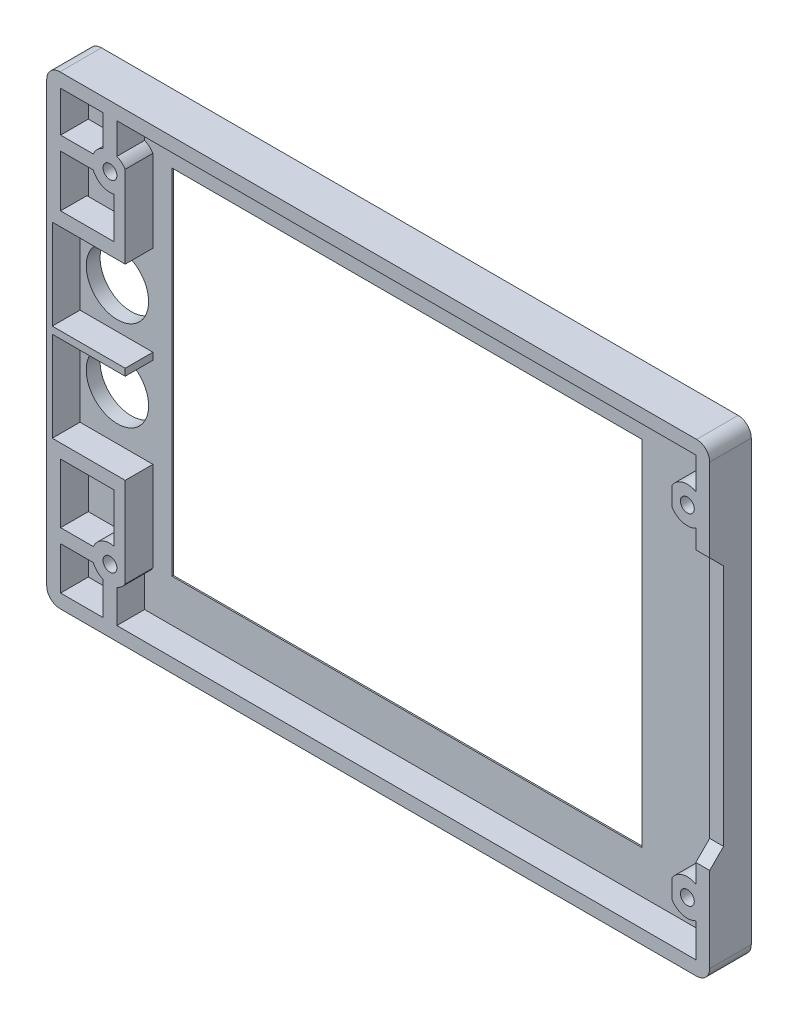
SolidWorks part; units mm, degrees
ref_plane "Спереди" through (0, 0, 0) normal (0, 0, 1) x (1, 0, 0)
ref_plane "Сверху" through (0, 0, 0) normal (0, 1, 0) x (1, 0, 0)
ref_plane "Справа" through (0, 0, 0) normal (1, 0, 0) x (0, 0, -1)
other "Configuration Table"
sketch "Эскиз1" plane through (0, 0, 0) normal (0, 0, 1) x (1, 0, 0)
  line L0 (-33.735, 25.6063) -> (34.065, 25.6063)
  line L1 (34.065, -25.3937) -> (34.065, 25.6063)
  line L2 (-45.825, 31.5375) -> (-45.825, 25.6776)
  line L3 (-39.7018, 31.5375) -> (-45.825, 31.5375)
  line L4 (-39.7018, 31.5375) -> (-39.7018, 27.0776)
  line L5 (-45.825, 23.6776) -> (-41.1018, 23.6776)
  line L6 (-45.825, 23.6776) -> (-45.825, 15.4128)
  line L7 (-37.1018, 22.6282) -> (-37.1018, 15.4128)
  line L8 (47.825, -31.6375) -> (47.825, -19.3686)
  line L9 (47.825, -19.3686) -> (45.825, -19.3686)
  line L10 (45.825, -19.3686) -> (45.825, -22.0746)
  line L11 (45.825, -26.6627) -> (45.825, -31.5375)
  line L12 (45.825, -31.5375) -> (-37.7018, -31.5375)
  line L13 (-37.7018, -31.5375) -> (-37.7018, -26.7686)
  line L14 (-36.1018, -24.3678) -> (-36.1018, 24.6776)
  line L15 (-37.7018, 27.0776) -> (-37.7018, 31.5375)
  line L16 (-37.7018, 31.5375) -> (45.825, 31.5375)
  line L17 (45.825, 31.5375) -> (45.825, 26.9716)
  line L18 (45.825, 22.3836) -> (45.825, 19.6776)
  line L19 (45.825, 19.6776) -> (47.825, 19.6776)
  line L20 (47.825, 19.6776) -> (47.825, 31.6375)
  line L21 (45.925, 33.5375) -> (-45.925, 33.5375)
  line L22 (-47.825, 31.6375) -> (-47.825, -31.6375)
  line L23 (-45.925, -33.5375) -> (45.925, -33.5375)
  line L24 (-37.1018, 15.4128) -> (-45.825, 15.4128)
  line L25 (-36.5018, 1.2128) -> (-47.025, 1.2128)
  line L26 (-47.025, 0.2057) -> (-36.5018, 0.2057)
  line L27 (-47.025, 14.2128) -> (-47.025, 1.2128)
  line L28 (-47.025, 0.2057) -> (-47.025, -12.7943)
  line L29 (-33.735, 25.6063) -> (-33.735, -25.3937)
  line L30 (34.065, -25.3937) -> (-33.735, -25.3937)
  line L31 (-47.025, -12.7943) -> (-36.5018, -12.7943)
  line L32 (-45.825, -13.9943) -> (-37.1018, -13.9943)
  line L33 (-45.825, -13.9943) -> (-45.825, -23.3686)
  line L34 (-41.1018, -23.3686) -> (-45.825, -23.3686)
  line L35 (-37.1018, -13.9943) -> (-37.1018, -22.3192)
  line L36 (-45.825, -25.3686) -> (-41.1018, -25.3686)
  line L37 (-45.825, -25.3686) -> (-45.825, -31.5375)
  line L38 (-39.7018, -26.7686) -> (-39.7018, -31.5375)
  line L39 (-45.825, -31.5375) -> (-39.7018, -31.5375)
  line L40 (45.825, 17.6776) -> (45.825, 19.6776)
  line L41 (47.825, 19.6776) -> (47.825, 17.6776)
  line L42 (45.825, 17.6776) -> (45.825, -17.3686)
  line L43 (45.825, -17.3686) -> (47.825, -17.3686)
  line L44 (47.825, -17.3686) -> (47.825, 17.6776)
  line L45 (47.825, 17.6776) -> (45.825, 17.6776)
  line L46 (45.825, -19.3686) -> (45.825, -17.3686)
  line L47 (47.825, -17.3686) -> (47.825, -19.3686)
  line L48 (-36.5018, 14.2128) -> (-47.025, 14.2128)
  circle A0 centre (44.6013, 24.6776) radius 1
  circle A1 centre (-38.7018, 24.6776) radius 1
  arc A2 (-39.7018, 27.0776) -> (-41.1018, 25.6776) centre (-38.7018, 24.6776) ccw
  arc A3 (-41.1018, 23.6776) -> (-37.1018, 22.6282) centre (-38.7018, 24.6776) ccw
  arc A4 (45.825, -22.0746) -> (45.825, -26.6627) centre (44.6013, -24.3686) ccw
  arc A5 (-37.7018, -26.7686) -> (-36.1018, -24.3678) centre (-38.7018, -24.3686) ccw
  arc A6 (-36.1018, 24.6776) -> (-37.7018, 27.0776) centre (-38.7018, 24.6776) ccw
  arc A7 (45.825, 26.9716) -> (45.825, 22.3836) centre (44.6013, 24.6776) ccw
  arc A8 (47.825, 31.6375) -> (45.925, 33.5375) centre (45.925, 31.6375) ccw
  arc A9 (-45.925, 33.5375) -> (-47.825, 31.6375) centre (-45.925, 31.6375) ccw
  arc A10 (-47.825, -31.6375) -> (-45.925, -33.5375) centre (-45.925, -31.6375) ccw
  arc A11 (45.925, -33.5375) -> (47.825, -31.6375) centre (45.925, -31.6375) ccw
  circle A12 centre (-41.625, 7.2128) radius 4.5
  circle A13 centre (-41.625, -5.7943) radius 4.5
  arc A14 (-37.1018, -22.3192) -> (-41.1018, -23.3686) centre (-38.7018, -24.3686) ccw
  circle A15 centre (-38.7018, -24.3686) radius 1
  arc A16 (-41.1018, -25.3686) -> (-39.7018, -26.7686) centre (-38.7018, -24.3686) ccw
  circle A17 centre (44.6013, -24.3686) radius 1
sketch "Эскиз2" plane through (0, 0, 0) normal (0, 0, 1) x (1, 0, 0)
  line L0 (34.065, -25.3937) -> (-33.735, -25.3937) construction
  line L1 (34.065, -25.3937) -> (34.065, 25.6063) construction
  line L2 (-33.735, 25.6063) -> (34.065, 25.6063) construction
  line L3 (-33.735, 25.6063) -> (-33.735, -25.3937) construction
  line L4 (-47.825, 31.6375) -> (-47.825, -31.6375) construction
  line L5 (-45.925, -33.5375) -> (45.925, -33.5375) construction
  line L6 (47.825, -31.6375) -> (47.825, -19.3686) construction
  line L7 (47.825, -17.3686) -> (47.825, 17.6776) construction
  line L8 (47.825, 19.6776) -> (47.825, 31.6375) construction
  line L9 (45.925, 33.5375) -> (-45.925, 33.5375) construction
  line L10 (34.065, -25.3937) -> (-33.735, -25.3937)
  line L11 (34.065, -25.3937) -> (34.065, 25.6063)
  line L12 (-33.735, 25.6063) -> (34.065, 25.6063)
  line L13 (-33.735, 25.6063) -> (-33.735, -25.3937)
  line L14 (-47.825, 31.6375) -> (-47.825, -31.6375)
  line L15 (-45.925, -33.5375) -> (45.925, -33.5375)
  line L16 (47.825, -31.6375) -> (47.825, -19.3686)
  line L17 (47.825, -17.3686) -> (47.825, 17.6776)
  line L18 (47.825, 19.6776) -> (47.825, 31.6375)
  line L19 (45.925, 33.5375) -> (-45.925, 33.5375)
  line L20 (47.825, 19.6776) -> (47.825, 17.6776) construction
  line L21 (47.825, 19.6776) -> (47.825, 17.6776)
  line L22 (47.825, -17.3686) -> (47.825, -19.3686) construction
  line L23 (47.825, -17.3686) -> (47.825, -19.3686)
  arc A0 (47.825, 31.6375) -> (45.925, 33.5375) centre (45.925, 31.6375) ccw construction
  arc A1 (47.825, 31.6375) -> (45.925, 33.5375) centre (45.925, 31.6375) ccw
  arc A2 (-45.925, 33.5375) -> (-47.825, 31.6375) centre (-45.925, 31.6375) ccw construction
  arc A3 (-45.925, 33.5375) -> (-47.825, 31.6375) centre (-45.925, 31.6375) ccw
  arc A4 (-47.825, -31.6375) -> (-45.925, -33.5375) centre (-45.925, -31.6375) ccw construction
  arc A5 (-47.825, -31.6375) -> (-45.925, -33.5375) centre (-45.925, -31.6375) ccw
  arc A6 (45.925, -33.5375) -> (47.825, -31.6375) centre (45.925, -31.6375) ccw construction
  arc A7 (45.925, -33.5375) -> (47.825, -31.6375) centre (45.925, -31.6375) ccw
  circle A8 centre (-41.625, 7.2128) radius 4.5 construction
  circle A9 centre (-41.625, 7.2128) radius 4.5
  circle A10 centre (-41.625, -5.7943) radius 4.5 construction
  circle A11 centre (-41.625, -5.7943) radius 4.5
extrude "Бобышка-Вытянуть1" add sketch "Эскиз2" along normal blind 2
sketch "Эскиз3" plane through (0, 0, 2) normal (0, 0, 1) x (1, 0, 0)
  line L0 (-45.825, 31.5375) -> (-45.825, 25.6776) construction
  line L1 (-39.7018, 31.5375) -> (-39.7018, 27.0776) construction
  line L2 (-39.7018, 31.5375) -> (-45.825, 31.5375) construction
  line L3 (-45.825, 31.5375) -> (-45.825, 25.6776)
  line L4 (45.925, 33.5375) -> (-45.925, 33.5375)
  line L5 (-47.825, 31.6375) -> (-47.825, -31.6375)
  line L6 (-45.925, -33.5375) -> (45.925, -33.5375)
  line L7 (47.825, -31.6375) -> (47.825, 31.6375)
  line L8 (45.925, 33.5375) -> (-45.925, 33.5375)
  line L9 (-47.825, 31.6375) -> (-47.825, -31.6375)
  line L10 (-45.925, -33.5375) -> (45.925, -33.5375)
  line L11 (47.825, -31.6375) -> (47.825, 31.6375)
  line L12 (-39.7018, 31.5375) -> (-39.7018, 27.0776)
  line L13 (-39.7018, 31.5375) -> (-45.825, 31.5375)
  line L14 (-45.825, 25.6776) -> (-41.1018, 25.6776)
  line L15 (-45.825, 23.6776) -> (-41.1018, 23.6776) construction
  line L16 (-45.825, 23.6776) -> (-45.825, 15.4128) construction
  line L17 (-37.1018, 15.4128) -> (-45.825, 15.4128) construction
  line L18 (-37.1018, 22.6282) -> (-37.1018, 15.4128) construction
  line L19 (-45.825, 23.6776) -> (-41.1018, 23.6776)
  line L20 (-45.825, 23.6776) -> (-45.825, 15.4128)
  line L21 (-37.1018, 15.4128) -> (-45.825, 15.4128)
  line L22 (-37.1018, 22.6282) -> (-37.1018, 15.4128)
  line L23 (-36.5018, 1.2128) -> (-47.025, 1.2128) construction
  line L24 (-47.025, 14.2128) -> (-47.025, 1.2128) construction
  line L25 (-36.5018, 14.2128) -> (-47.025, 14.2128) construction
  line L26 (-36.5018, 1.2128) -> (-47.025, 1.2128)
  line L27 (-47.025, 14.2128) -> (-47.025, 1.2128)
  line L28 (-36.5018, 14.2128) -> (-47.025, 14.2128)
  line L30 (-36.1018, 14.2128) -> (-36.1018, 1.2128)
  line L31 (-36.5018, 14.2128) -> (-36.1018, 14.2128)
  line L32 (-36.5018, 1.2128) -> (-36.1018, 1.2128)
  line L33 (-36.5018, 0.2057) -> (-36.1018, 0.2057)
  line L34 (-47.025, 0.2057) -> (-47.025, -12.7943) construction
  line L35 (-47.025, 0.2057) -> (-36.5018, 0.2057) construction
  line L36 (-47.025, 0.2057) -> (-47.025, -12.7943)
  line L37 (-47.025, 0.2057) -> (-36.5018, 0.2057)
  line L38 (-47.025, -12.7943) -> (-36.5018, -12.7943) construction
  line L39 (-47.025, -12.7943) -> (-36.5018, -12.7943)
  line L40 (-36.5018, -12.7943) -> (-36.1018, -12.7943)
  line L41 (-36.1018, 0.2057) -> (-36.1018, -12.7943)
  line L42 (-41.1018, -23.3686) -> (-45.825, -23.3686) construction
  line L43 (-45.825, -13.9943) -> (-45.825, -23.3686) construction
  line L44 (-37.1018, -13.9943) -> (-37.1018, -22.3192) construction
  line L45 (-45.825, -13.9943) -> (-37.1018, -13.9943) construction
  line L46 (-41.1018, -23.3686) -> (-45.825, -23.3686)
  line L47 (-45.825, -13.9943) -> (-45.825, -23.3686)
  line L48 (-37.1018, -13.9943) -> (-37.1018, -22.3192)
  line L49 (-45.825, -13.9943) -> (-37.1018, -13.9943)
  line L50 (-36.1018, 1.2128) -> (-36.1018, 0.2057)
  line L51 (-36.1018, 24.6776) -> (-36.1018, 14.2128)
  line L52 (-36.1018, -12.7943) -> (-36.1018, -24.3678)
  line L53 (-39.7018, -26.7686) -> (-39.7018, -31.5375) construction
  line L54 (-45.825, -31.5375) -> (-39.7018, -31.5375) construction
  line L55 (-45.825, -25.3686) -> (-45.825, -31.5375) construction
  line L56 (-45.825, -25.3686) -> (-41.1018, -25.3686) construction
  line L57 (-39.7018, -26.7686) -> (-39.7018, -31.5375)
  line L58 (-45.825, -31.5375) -> (-39.7018, -31.5375)
  line L59 (-45.825, -25.3686) -> (-45.825, -31.5375)
  line L60 (-45.825, -25.3686) -> (-41.1018, -25.3686)
  line L61 (45.825, -31.5375) -> (-37.7018, -31.5375) construction
  line L62 (-37.7018, -31.5375) -> (-37.7018, -26.7686) construction
  line L63 (45.825, -31.5375) -> (-37.7018, -31.5375)
  line L64 (-37.7018, -31.5375) -> (-37.7018, -26.7686)
  line L65 (45.825, -26.6627) -> (45.825, -31.5375) construction
  line L66 (45.825, -26.6627) -> (45.825, -31.5375)
  line L67 (45.825, 17.6776) -> (45.825, -17.3686) construction
  line L68 (45.825, -19.3686) -> (45.825, -17.3686) construction
  line L69 (45.825, -19.3686) -> (45.825, -22.0746) construction
  line L70 (45.825, 17.6776) -> (45.825, -17.3686)
  line L71 (45.825, -19.3686) -> (45.825, -17.3686)
  line L72 (45.825, -19.3686) -> (45.825, -22.0746)
  line L73 (45.825, 17.6776) -> (45.825, 19.6776) construction
  line L74 (45.825, 22.3836) -> (45.825, 19.6776) construction
  line L75 (45.825, 31.5375) -> (45.825, 26.9716) construction
  line L76 (45.825, 17.6776) -> (45.825, 19.6776)
  line L77 (45.825, 22.3836) -> (45.825, 19.6776)
  line L78 (45.825, 31.5375) -> (45.825, 26.9716)
  line L79 (-37.7018, 31.5375) -> (45.825, 31.5375) construction
  line L80 (-37.7018, 31.5375) -> (45.825, 31.5375)
  line L81 (-37.7018, 27.0776) -> (-37.7018, 31.5375) construction
  line L82 (-37.7018, 27.0776) -> (-37.7018, 31.5375)
  arc A0 (-39.7018, 27.0776) -> (-41.1018, 25.6776) centre (-38.7018, 24.6776) ccw construction
  arc A1 (-39.7018, 27.0776) -> (-41.1018, 25.6776) centre (-38.7018, 24.6776) ccw
  circle A2 centre (-38.7018, 24.6776) radius 1 construction
  circle A3 centre (-38.7018, 24.6776) radius 1
  arc A4 (47.825, 31.6375) -> (45.925, 33.5375) centre (45.925, 31.6375) ccw
  arc A5 (-45.925, 33.5375) -> (-47.825, 31.6375) centre (-45.925, 31.6375) ccw
  arc A6 (-47.825, -31.6375) -> (-45.925, -33.5375) centre (-45.925, -31.6375) ccw
  arc A7 (45.925, -33.5375) -> (47.825, -31.6375) centre (45.925, -31.6375) ccw
  arc A8 (47.825, 31.6375) -> (45.925, 33.5375) centre (45.925, 31.6375) ccw
  arc A9 (-45.925, 33.5375) -> (-47.825, 31.6375) centre (-45.925, 31.6375) ccw
  arc A10 (-47.825, -31.6375) -> (-45.925, -33.5375) centre (-45.925, -31.6375) ccw
  arc A11 (45.925, -33.5375) -> (47.825, -31.6375) centre (45.925, -31.6375) ccw
  arc A12 (-41.1018, 23.6776) -> (-37.1018, 22.6282) centre (-38.7018, 24.6776) ccw construction
  arc A13 (-41.1018, 23.6776) -> (-37.1018, 22.6282) centre (-38.7018, 24.6776) ccw
  circle A14 centre (-38.7018, -24.3686) radius 1 construction
  arc A15 (-37.1018, -22.3192) -> (-41.1018, -23.3686) centre (-38.7018, -24.3686) ccw construction
  circle A16 centre (-38.7018, -24.3686) radius 1
  arc A17 (-37.1018, -22.3192) -> (-41.1018, -23.3686) centre (-38.7018, -24.3686) ccw
  arc A18 (-37.7018, -26.7686) -> (-36.1018, -24.3678) centre (-38.7018, -24.3686) ccw construction
  arc A19 (-37.7018, -26.7686) -> (-36.1018, -24.3678) centre (-38.7018, -24.3686) ccw
  arc A20 (-41.1018, -25.3686) -> (-39.7018, -26.7686) centre (-38.7018, -24.3686) ccw construction
  arc A21 (-41.1018, -25.3686) -> (-39.7018, -26.7686) centre (-38.7018, -24.3686) ccw
  circle A22 centre (44.6013, -24.3686) radius 1 construction
  arc A23 (45.825, -22.0746) -> (45.825, -26.6627) centre (44.6013, -24.3686) ccw construction
  circle A24 centre (44.6013, -24.3686) radius 1
  arc A25 (45.825, -22.0746) -> (45.825, -26.6627) centre (44.6013, -24.3686) ccw
  circle A26 centre (44.6013, 24.6776) radius 1 construction
  arc A27 (45.825, 26.9716) -> (45.825, 22.3836) centre (44.6013, 24.6776) ccw construction
  circle A28 centre (44.6013, 24.6776) radius 1
  arc A29 (45.825, 26.9716) -> (45.825, 22.3836) centre (44.6013, 24.6776) ccw
  arc A30 (-36.1018, 24.6776) -> (-37.7018, 27.0776) centre (-38.7018, 24.6776) ccw construction
  arc A31 (-36.1018, 24.6776) -> (-37.7018, 27.0776) centre (-38.7018, 24.6776) ccw
  arc M37 (47.825, 31.6375) -> (45.925, 33.5375) centre (45.925, 31.6375) ccw
  line M38 (45.925, 33.5375) -> (-45.925, 33.5375)
  arc M39 (-45.925, 33.5375) -> (-47.825, 31.6375) centre (-45.925, 31.6375) ccw
  line M40 (-47.825, 31.6375) -> (-47.825, -31.6375)
  arc M41 (-47.825, -31.6375) -> (-45.925, -33.5375) centre (-45.925, -31.6375) ccw
  line M42 (-45.925, -33.5375) -> (45.925, -33.5375)
  arc M43 (45.925, -33.5375) -> (47.825, -31.6375) centre (45.925, -31.6375) ccw
  line M44 (47.825, -31.6375) -> (47.825, 31.6375)
  dimension "D1" = 0
extrude "Бобышка-Вытянуть2" add sketch "Эскиз3" along normal blind 4 contours L60 A21 L57 L58 L59 L48 A17 L46 L47 L49 L19 A13 L22 L21 L20 L12 A1 L14 L3 L13 A3 A16 A24 A28 L51 A31 L82 L80 L78 A29 L77 L76 L70 L71 M44 M37 M38 M39 M40 M41 M42 M43 region at (46.4424, 32.1549, 2)
sketch "Эскиз4" plane through (0, 0, 6) normal (0, 0, 1) x (1, 0, 0)
  line L0 (-45.825, -13.9943) -> (-45.825, -23.3686) construction
  line L1 (-36.1018, 14.2128) -> (-38.1018, 14.2128)
  line L2 (-36.1018, 14.2128) -> (-36.1018, 23.2128)
  line L3 (-36.1018, 23.2128) -> (-38.1018, 23.2128)
  line L4 (-38.1018, 14.2128) -> (-38.1018, 23.2128)
  line L5 (-36.1018, -12.7943) -> (-38.1018, -12.7943)
  line L6 (-36.1018, -12.7943) -> (-36.1018, -22.7943)
  line L7 (-36.1018, -22.7943) -> (-38.1018, -22.7943)
  line L8 (-38.1018, -12.7943) -> (-38.1018, -22.7943)
  line L9 (-38.1018, -12.7943) -> (-45.825, -12.7943)
  line L10 (-38.1018, -12.7943) -> (-38.1018, -14.7943)
  line L11 (-38.1018, -14.7943) -> (-45.825, -14.7943)
  line L12 (-45.825, -12.7943) -> (-45.825, -14.7943)
  line L13 (-45.825, 23.6776) -> (-45.825, 15.4128) construction
  line L14 (-38.1018, 14.2128) -> (-45.825, 14.2128)
  line L15 (-38.1018, 14.2128) -> (-38.1018, 16.2128)
  line L16 (-38.1018, 16.2128) -> (-45.825, 16.2128)
  line L17 (-45.825, 14.2128) -> (-45.825, 16.2128)
  dimension "D1" = 2
  dimension "D2" = 9
  dimension "D3" = 2
  dimension "D4" = 10
  dimension "D5" = 2
  dimension "D6" = 2
extrude "Бобышка-Вытянуть3" add sketch "Эскиз4" against normal blind 3.8 contours L17 L14 L4 L16 | L4 L1 L2 L3 | L9 L12 L11 L8 | L5 L8 L7 L6 region at (-37.1018, 18.7128, 6) region at (-41.9634, 15.2128, 6) region at (-37.1018, -17.7943, 6) region at (-41.9634, -13.7943, 6)
sketch "Эскиз5" plane through (0, 0, 6) normal (0, 0, 1) x (1, 0, 0)
  line L0 (47.825, -17.3686) -> (47.825, -19.3686) construction
  line L1 (47.825, -19.3686) -> (45.825, -19.3686) construction
  line L2 (45.825, -19.3686) -> (45.825, -17.3686) construction
  line L3 (47.825, 19.6776) -> (47.825, 17.6776) construction
  line L4 (45.825, 17.6776) -> (45.825, 19.6776) construction
  line L5 (45.825, 17.6776) -> (45.825, -17.3686) construction
  line L6 (47.825, -17.3686) -> (47.825, 17.6776) construction
  line L7 (45.825, 19.6776) -> (47.825, 19.6776) construction
  line L8 (47.825, -17.3686) -> (47.825, -19.3686)
  line L9 (47.825, -19.3686) -> (45.825, -19.3686)
  line L10 (45.825, -19.3686) -> (45.825, -17.3686)
  line L11 (47.825, 19.6776) -> (47.825, 17.6776)
  line L12 (45.825, 17.6776) -> (45.825, 19.6776)
  line L13 (45.825, 17.6776) -> (45.825, -17.3686)
  line L14 (47.825, -17.3686) -> (47.825, 17.6776)
  line L15 (45.825, 19.6776) -> (47.825, 19.6776)
extrude "Вырез-Вытянуть1" cut sketch "Эскиз5" against normal blind 2
chamfer "Фаска2" distance 2 angle 45 2 edges at (46.825, 19.6776, 4) (46.825, -19.3686, 4)
sketch "Эскиз6" plane through (0, 0, 2) normal (0, 0, 1) x (1, 0, 0)
  line L0 (-37.7018, 31.5375) -> (45.825, 31.5375) construction
  line L1 (-36.5018, 30.5375) -> (42.4013, 30.5375)
  line L2 (-36.5018, 30.5375) -> (-36.5018, -29.5375)
  line L3 (-36.5018, -29.5375) -> (42.4013, -29.5375)
  line L4 (42.4013, 30.5375) -> (42.4013, -29.5375)
  line L5 (-36.1018, 24.6776) -> (-36.1018, 14.2128) construction
  line L6 (45.825, -31.5375) -> (-37.7018, -31.5375) construction
  arc A0 (45.825, 26.9716) -> (45.825, 22.3836) centre (44.6013, 24.6776) ccw construction
  dimension "D1" = 1
  dimension "D2" = 0.4
  dimension "D3" = 2
  dimension "D4" = 2.2
extrude "Вырез-Вытянуть2" cut sketch "Эскиз6" along normal blind 4
sketch "button_holes" plane through (0, 0, 0) normal (0, 0, -1) x (-1, 0, 0)
  circle A0 centre (41.625, -5.7943) radius 4.5 construction
  circle A1 centre (41.625, 7.2128) radius 4.5 construction
  circle A2 centre (41.625, -5.7943) radius 4.5
  circle A3 centre (41.625, 7.2128) radius 4.5
chamfer "Фаска3" distance 1.8 angle 45 4 edges at (-33.735, 0.1063, 0) (0.165, 25.6063, 0) (34.065, 0.1063, 0) (0.165, -25.3937, 0)
